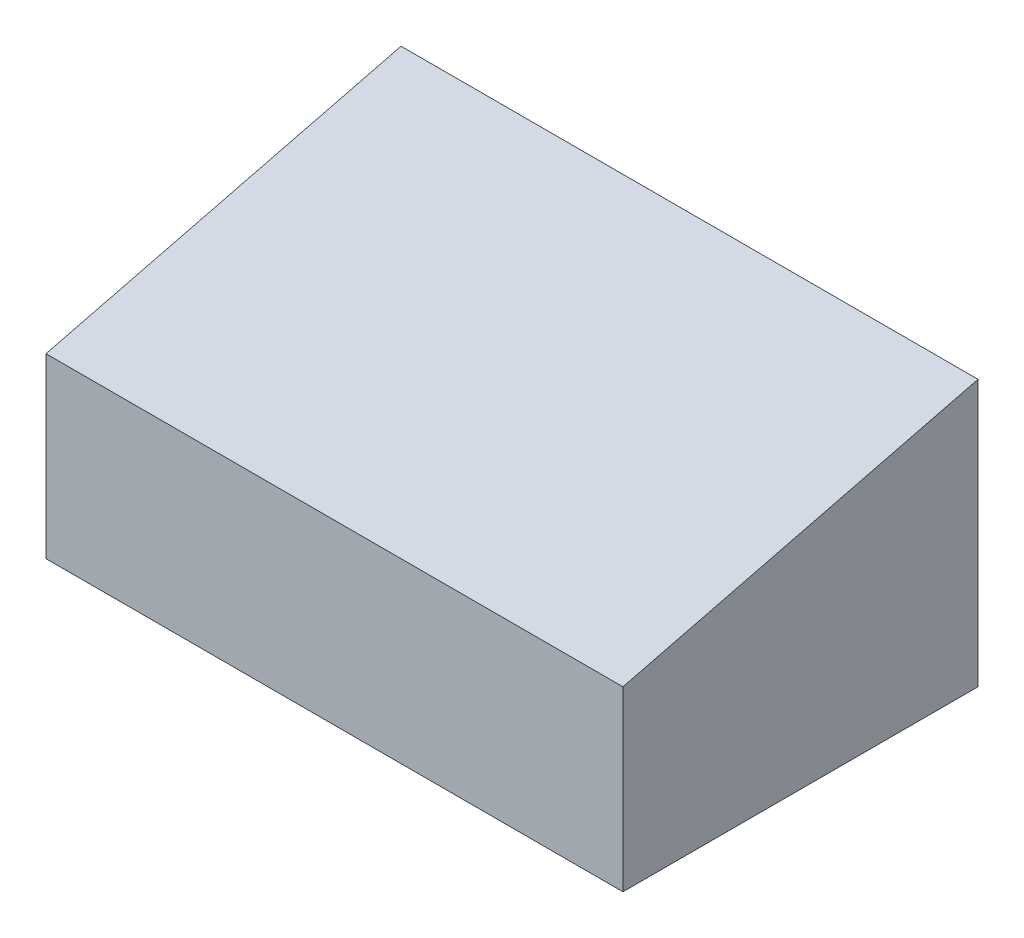
SolidWorks part; units mm, degrees
ref_plane "Front Plane" through (0, 0, 0) normal (0, 0, 1) x (1, 0, 0)
ref_plane "Top Plane" through (0, 0, 0) normal (0, 1, 0) x (1, 0, 0)
ref_plane "Right Plane" through (0, 0, 0) normal (1, 0, 0) x (0, 0, -1)
sketch "Sketch1" plane through (0, 0, 0) normal (0, 1, 0) x (1, 0, 0)
  line L1 (-65, 40) -> (65, 40)
  line L2 (-65, 40) -> (-65, -40)
  line L3 (-65, -40) -> (65, -40)
  line L4 (65, 40) -> (65, -40)
  line L5 (-65, 40) -> (65, -40) construction
  line L6 (-65, -40) -> (65, 40) construction
  point P0 (0, 0)
  dimension "D1" = 130
  dimension "D2" = 80
extrude "Boss-Extrude1" add sketch "Sketch1" along normal blind 60
chamfer "Chamfer1" distance 20 distance2 80 1 edges at (0, 60, 40) first distance on face at (0, 30, 40)
